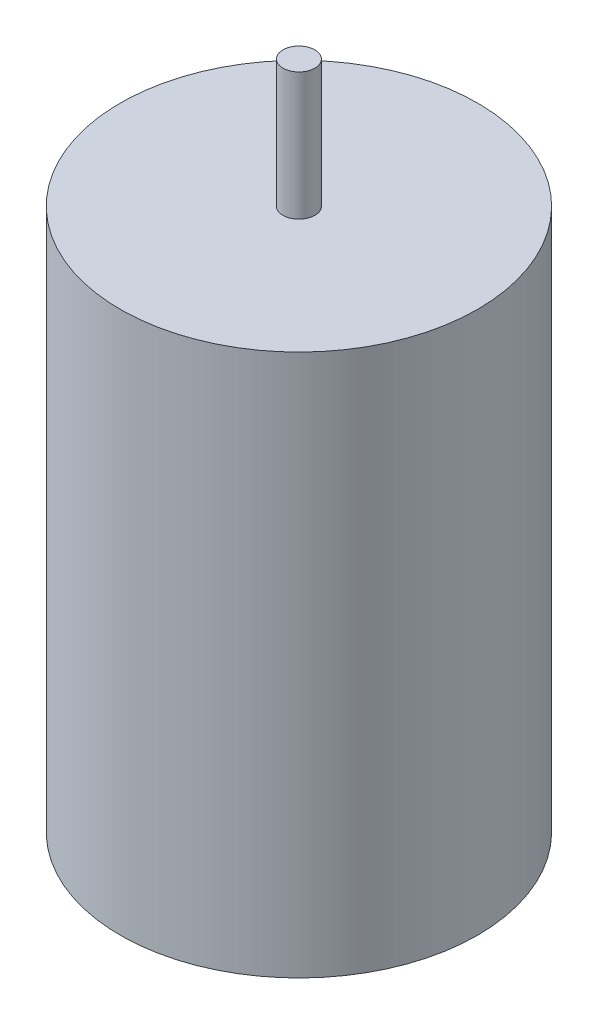
SolidWorks part; units mm, degrees
ref_plane "Front Plane" through (0, 0, 0) normal (0, 0, 1) x (1, 0, 0)
ref_plane "Top Plane" through (0, 0, 0) normal (0, 1, 0) x (1, 0, 0)
ref_plane "Right Plane" through (0, 0, 0) normal (1, 0, 0) x (0, 0, -1)
sketch "Sketch1" plane through (0, 0, 0) normal (0, 0, 1) x (1, 0, 0)
  line L0 (0, -66.7) -> (0, 66.7) construction
  line L1 (0, 66.7) -> (1.585, 66.7)
  line L2 (1.585, 66.7) -> (1.585, 54)
  line L3 (1.585, 54) -> (17.8, 54)
  line L4 (17.8, 54) -> (17.8, 0)
  line L5 (17.8, 0) -> (0, 0)
  line L6 (0, 66.7) -> (0, 0)
  point P0 (0, 69.3604)
  point P4 (0, 0)
  dimension "D1" = 54
  dimension "D2" = 35.6
  dimension "D3" = 3.17
  dimension "D4" = 12.7
revolve "Revolve1" add sketch "Sketch1" angle 360 about L0
